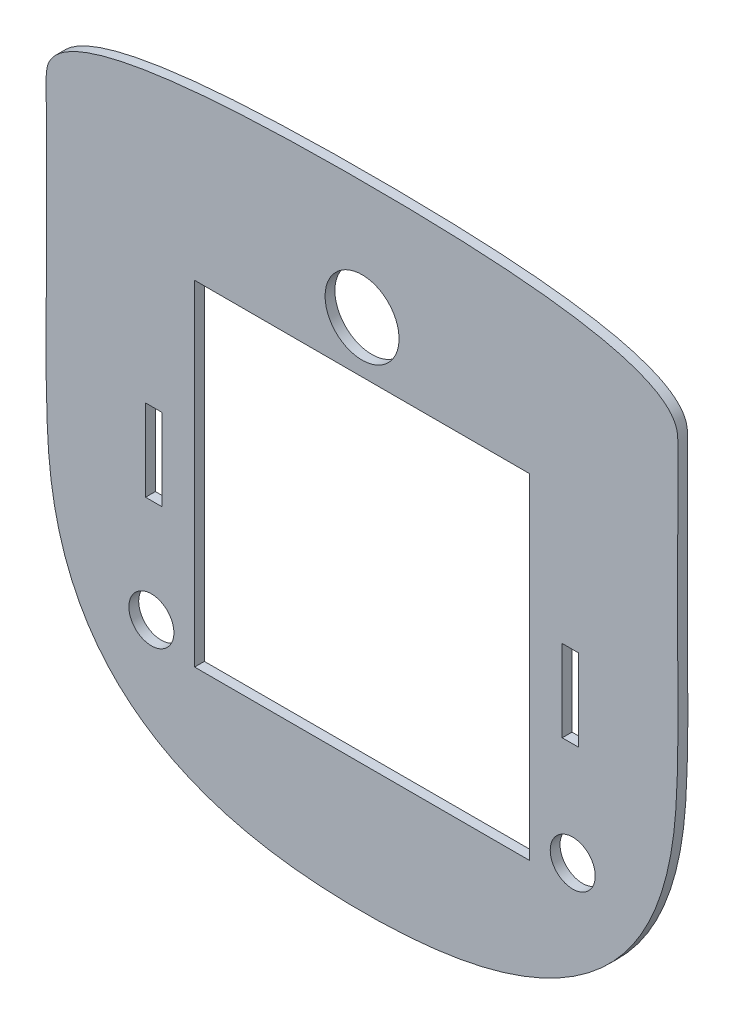
SolidWorks part; units mm, degrees
ref_plane "Front Plane" through (0, 0, 0) normal (0, 0, 1) x (1, 0, 0)
ref_plane "Top Plane" through (0, 0, 0) normal (0, 1, 0) x (1, 0, 0)
ref_plane "Right Plane" through (0, 0, 0) normal (1, 0, 0) x (0, 0, -1)
sketch "Sketch2" plane through (-0.2017, -72.2355, -2871.2971) normal (0, 0, 1) x (1, 0, 0)
  line L0 (52.07, 67.2522) -> (-52.07, 67.2522) construction
  line L1 (-52.07, 67.2522) -> (-52.07, -36.8878) construction
  line L2 (52.07, -36.8878) -> (52.07, 67.2522) construction
  line L3 (-52.07, -36.8878) -> (52.07, -36.8878) construction
  line L4 (52.07, 67.2522) -> (-52.07, 67.2522)
  line L5 (-52.07, 67.2522) -> (-52.07, -36.8878)
  line L6 (52.07, -36.8878) -> (52.07, 67.2522)
  line L7 (-52.07, -36.8878) -> (52.07, -36.8878)
  line L8 (0, 67.2522) -> (0, 47.5498)
  line L9 (-67.31, 26.6122) -> (-62.23, 26.6122)
  line L10 (-67.31, 26.6122) -> (-67.31, 1.2122)
  line L11 (-67.31, 1.2122) -> (-62.23, 1.2122)
  line L12 (-62.23, 26.6122) -> (-62.23, 1.2122)
  line L13 (67.31, 1.2122) -> (62.23, 1.2122)
  line L14 (67.31, 26.6122) -> (62.23, 26.6122)
  line L15 (62.23, 26.6122) -> (62.23, 1.2122)
  line L16 (67.31, 26.6122) -> (67.31, 1.2122)
  circle A0 centre (65.5, -30.8878) radius 7 construction
  circle A1 centre (-65.5, -30.8878) radius 7 construction
  circle A2 centre (0, 83.2872) radius 11.5 construction
  circle A3 centre (65.5, -30.8878) radius 7
  circle A4 centre (-65.5, -30.8878) radius 7
  circle A5 centre (0, 83.2872) radius 11.5
  spline S0 degree 3 poles (97.9117, 101.757) (98.0926, 100.5826) (98.1683, 99.8507) (98.201, 98.9643) (98.2056, 98.5204) (98.2033, 98.0762) (98.2036, 97.6318) (98.2026, 97.1872) (98.2018, 96.5942) (98.1997, 95.5557) (98.1964, 94.0701) (98.1912, 92.2844) (98.1853, 90.4955) (98.1786, 88.7035) (98.1713, 86.9085) (98.1636, 85.1105) (98.1554, 83.3094) (98.147, 81.5054) (98.1356, 79.096) (98.1213, 76.0769) (98.1051, 72.4424) (98.0908, 68.7965) (98.0796, 65.1394) (98.0728, 61.4713) (98.0711, 57.7925) (98.0753, 54.103) (98.0874, 50.4033) (98.1094, 46.6935) (98.1491, 41.7343) (98.2125, 35.5119) (98.2598, 28.01) (98.2502, 21.7312) (98.1939, 16.6943) (98.1345, 13.5409) (98.0699, 11.0154) (98.0125, 9.1199) (97.945, 7.2235) (97.8675, 5.3262) (97.778, 3.4282) (97.6786, 1.5298) (97.5624, -0.3688) (97.2739, -4.1659) (96.6367, -9.8576) (95.2643, -17.3922) (93.2832, -24.8169) (90.6142, -32.0401) (87.1877, -38.9585) (83.6766, -44.3599) (80.4862, -48.4025) (77.0545, -52.2409) (72.332, -56.6273) (66.103, -61.1882) (59.4287, -65.0467) (52.4324, -68.2445) (45.1957, -70.832) (37.7973, -72.8633) (30.2897, -74.3932) (22.7275, -75.4943) (12.6127, -76.4627) (5.0324, -76.7148) (-5.0355, -76.7148) (-12.6198, -76.4624) (-22.7388, -75.4931) (-30.3035, -74.391) (-37.8129, -72.8599) (-45.2125, -70.8272) (-52.4499, -68.238) (-59.4461, -65.0384) (-66.1196, -61.178) (-72.3471, -56.6154) (-77.0679, -52.2278) (-80.4981, -48.3887) (-83.6868, -44.3454) (-87.1957, -38.9438) (-90.6199, -32.0257) (-93.2868, -24.8034) (-95.2663, -17.38) (-96.6374, -9.847) (-97.2741, -4.1565) (-97.5622, -0.3603) (-97.6784, 1.5379) (-97.7779, 3.4359) (-97.8674, 5.3334) (-97.9449, 7.2303) (-98.0124, 9.1263) (-98.0698, 11.0213) (-98.1344, 13.5463) (-98.1939, 16.699) (-98.2502, 21.7349) (-98.2598, 28.0124) (-98.2124, 35.5129) (-98.1491, 41.7344) (-98.1094, 46.6929) (-98.0874, 50.4022) (-98.0753, 54.1015) (-98.0711, 57.7907) (-98.0728, 61.4693) (-98.0796, 65.1372) (-98.0908, 68.7942) (-98.1051, 72.44) (-98.1213, 76.0745) (-98.1356, 79.0937) (-98.147, 81.5032) (-98.1554, 83.3073) (-98.1636, 85.1085) (-98.1713, 86.9067) (-98.1786, 88.7018) (-98.1853, 90.494) (-98.1912, 92.283) (-98.1963, 94.069) (-98.1997, 95.5548) (-98.2018, 96.5934) (-98.2026, 97.1865) (-98.2036, 97.6312) (-98.2034, 98.0756) (-98.2056, 98.5199) (-98.201, 98.9639) (-98.1685, 99.8505) (-98.0927, 100.5825) (-97.9118, 101.7567) (-97.5911, 102.9272) (-96.7445, 104.5237) (-95.6284, 105.9307) (-94.3242, 107.1498) (-92.9089, 108.2104) (-90.9195, 109.4482) (-88.322, 110.7311) (-85.1289, 111.981) (-81.907, 113.0191) (-78.6797, 113.8993) (-75.4586, 114.6561) (-72.2483, 115.315) (-69.0513, 115.893) (-65.8677, 116.4036) (-62.6974, 116.856) (-59.5401, 117.2586) (-55.346, 117.7364) (-50.1305, 118.2378) (-43.9049, 118.7183) (-37.6983, 119.1001) (-31.4972, 119.4014) (-25.2861, 119.6319) (-19.0497, 119.8026) (-10.6783, 119.9573) (-4.3114, 120) (4.3116, 120) (10.6784, 119.9573) (19.0492, 119.8026) (25.285, 119.6319) (31.4954, 119.4014) (37.6957, 119.1003) (43.9016, 118.7185) (50.1264, 118.2381) (55.3414, 117.7368) (59.535, 117.2592) (62.6921, 116.8566) (65.8622, 116.4044) (69.0457, 115.8939) (72.2427, 115.316) (75.4529, 114.6572) (78.6742, 113.9005) (81.9018, 113.0204) (85.1241, 111.9825) (88.3177, 110.7327) (90.916, 109.4498) (92.906, 108.212) (94.3218, 107.1513) (95.6266, 105.9321) (96.7434, 104.5248) (97.5906, 102.9279) (97.9117, 101.757) (98.0926, 100.5826) (98.1683, 99.8507) knots -0.005356 -0.002678 0 0 0.002568 0.00321 0.003852 0.004494 0.005135 0.005777 0.006419 0.007703 0.010271 0.012839 0.015406 0.017974 0.020542 0.02311 0.025677 0.028245 0.030813 0.035948 0.041084 0.046219 0.051355 0.05649 0.061626 0.066761 0.071897 0.077032 0.082168 0.092439 0.10271 0.112981 0.118116 0.123252 0.125819 0.128387 0.130955 0.133522 0.13609 0.138658 0.141226 0.143793 0.154064 0.164335 0.174606 0.184877 0.195148 0.205419 0.210555 0.21569 0.225961 0.236232 0.246503 0.256774 0.267045 0.277316 0.287587 0.297858 0.308129 0.328671 0.328671 0.349207 0.359475 0.369743 0.380011 0.390279 0.400547 0.410816 0.421084 0.431352 0.44162 0.446754 0.451888 0.462156 0.472424 0.482692 0.492961 0.503229 0.513497 0.516064 0.518631 0.521198 0.523765 0.526332 0.528899 0.531466 0.534033 0.539167 0.544301 0.554569 0.564837 0.575105 0.580239 0.585374 0.590508 0.595642 0.600776 0.60591 0.611044 0.616178 0.621312 0.626446 0.629013 0.63158 0.634147 0.636714 0.639281 0.641848 0.644415 0.646982 0.649549 0.650833 0.651475 0.652116 0.652758 0.6534 0.654042 0.654683 0.65725 0.65725 0.659928 0.662606 0.665283 0.667961 0.670639 0.673317 0.678672 0.684027 0.689383 0.694738 0.700094 0.705449 0.710804 0.71616 0.721515 0.726871 0.732226 0.742937 0.753648 0.764359 0.775069 0.78578 0.796491 0.807202 0.828623 0.828623 0.850045 0.860757 0.871468 0.882179 0.89289 0.903601 0.914312 0.925023 0.930378 0.935734 0.941089 0.946445 0.9518 0.957156 0.962511 0.967867 0.973222 0.978578 0.983933 0.986611 0.989289 0.991967 0.994644 0.997322 1 1 1.002568 1.00321 1.003852 only from (98.0041, 101.1575) to (98.0041, 101.1575)
  spline S1 degree 3 poles (97.9117, 101.757) (98.0926, 100.5826) (98.1683, 99.8507) (98.201, 98.9643) (98.2056, 98.5204) (98.2033, 98.0762) (98.2036, 97.6318) (98.2026, 97.1872) (98.2018, 96.5942) (98.1997, 95.5557) (98.1964, 94.0701) (98.1912, 92.2844) (98.1853, 90.4955) (98.1786, 88.7035) (98.1713, 86.9085) (98.1636, 85.1105) (98.1554, 83.3094) (98.147, 81.5054) (98.1356, 79.096) (98.1213, 76.0769) (98.1051, 72.4424) (98.0908, 68.7965) (98.0796, 65.1394) (98.0728, 61.4713) (98.0711, 57.7925) (98.0753, 54.103) (98.0874, 50.4033) (98.1094, 46.6935) (98.1491, 41.7343) (98.2125, 35.5119) (98.2598, 28.01) (98.2502, 21.7312) (98.1939, 16.6943) (98.1345, 13.5409) (98.0699, 11.0154) (98.0125, 9.1199) (97.945, 7.2235) (97.8675, 5.3262) (97.778, 3.4282) (97.6786, 1.5298) (97.5624, -0.3688) (97.2739, -4.1659) (96.6367, -9.8576) (95.2643, -17.3922) (93.2832, -24.8169) (90.6142, -32.0401) (87.1877, -38.9585) (83.6766, -44.3599) (80.4862, -48.4025) (77.0545, -52.2409) (72.332, -56.6273) (66.103, -61.1882) (59.4287, -65.0467) (52.4324, -68.2445) (45.1957, -70.832) (37.7973, -72.8633) (30.2897, -74.3932) (22.7275, -75.4943) (12.6127, -76.4627) (5.0324, -76.7148) (-5.0355, -76.7148) (-12.6198, -76.4624) (-22.7388, -75.4931) (-30.3035, -74.391) (-37.8129, -72.8599) (-45.2125, -70.8272) (-52.4499, -68.238) (-59.4461, -65.0384) (-66.1196, -61.178) (-72.3471, -56.6154) (-77.0679, -52.2278) (-80.4981, -48.3887) (-83.6868, -44.3454) (-87.1957, -38.9438) (-90.6199, -32.0257) (-93.2868, -24.8034) (-95.2663, -17.38) (-96.6374, -9.847) (-97.2741, -4.1565) (-97.5622, -0.3603) (-97.6784, 1.5379) (-97.7779, 3.4359) (-97.8674, 5.3334) (-97.9449, 7.2303) (-98.0124, 9.1263) (-98.0698, 11.0213) (-98.1344, 13.5463) (-98.1939, 16.699) (-98.2502, 21.7349) (-98.2598, 28.0124) (-98.2124, 35.5129) (-98.1491, 41.7344) (-98.1094, 46.6929) (-98.0874, 50.4022) (-98.0753, 54.1015) (-98.0711, 57.7907) (-98.0728, 61.4693) (-98.0796, 65.1372) (-98.0908, 68.7942) (-98.1051, 72.44) (-98.1213, 76.0745) (-98.1356, 79.0937) (-98.147, 81.5032) (-98.1554, 83.3073) (-98.1636, 85.1085) (-98.1713, 86.9067) (-98.1786, 88.7018) (-98.1853, 90.494) (-98.1912, 92.283) (-98.1963, 94.069) (-98.1997, 95.5548) (-98.2018, 96.5934) (-98.2026, 97.1865) (-98.2036, 97.6312) (-98.2034, 98.0756) (-98.2056, 98.5199) (-98.201, 98.9639) (-98.1685, 99.8505) (-98.0927, 100.5825) (-97.9118, 101.7567) (-97.5911, 102.9272) (-96.7445, 104.5237) (-95.6284, 105.9307) (-94.3242, 107.1498) (-92.9089, 108.2104) (-90.9195, 109.4482) (-88.322, 110.7311) (-85.1289, 111.981) (-81.907, 113.0191) (-78.6797, 113.8993) (-75.4586, 114.6561) (-72.2483, 115.315) (-69.0513, 115.893) (-65.8677, 116.4036) (-62.6974, 116.856) (-59.5401, 117.2586) (-55.346, 117.7364) (-50.1305, 118.2378) (-43.9049, 118.7183) (-37.6983, 119.1001) (-31.4972, 119.4014) (-25.2861, 119.6319) (-19.0497, 119.8026) (-10.6783, 119.9573) (-4.3114, 120) (4.3116, 120) (10.6784, 119.9573) (19.0492, 119.8026) (25.285, 119.6319) (31.4954, 119.4014) (37.6957, 119.1003) (43.9016, 118.7185) (50.1264, 118.2381) (55.3414, 117.7368) (59.535, 117.2592) (62.6921, 116.8566) (65.8622, 116.4044) (69.0457, 115.8939) (72.2427, 115.316) (75.4529, 114.6572) (78.6742, 113.9005) (81.9018, 113.0204) (85.1241, 111.9825) (88.3177, 110.7327) (90.916, 109.4498) (92.906, 108.212) (94.3218, 107.1513) (95.6266, 105.9321) (96.7434, 104.5248) (97.5906, 102.9279) (97.9117, 101.757) (98.0926, 100.5826) (98.1683, 99.8507) knots -0.005356 -0.002678 0 0 0.002568 0.00321 0.003852 0.004494 0.005135 0.005777 0.006419 0.007703 0.010271 0.012839 0.015406 0.017974 0.020542 0.02311 0.025677 0.028245 0.030813 0.035948 0.041084 0.046219 0.051355 0.05649 0.061626 0.066761 0.071897 0.077032 0.082168 0.092439 0.10271 0.112981 0.118116 0.123252 0.125819 0.128387 0.130955 0.133522 0.13609 0.138658 0.141226 0.143793 0.154064 0.164335 0.174606 0.184877 0.195148 0.205419 0.210555 0.21569 0.225961 0.236232 0.246503 0.256774 0.267045 0.277316 0.287587 0.297858 0.308129 0.328671 0.328671 0.349207 0.359475 0.369743 0.380011 0.390279 0.400547 0.410816 0.421084 0.431352 0.44162 0.446754 0.451888 0.462156 0.472424 0.482692 0.492961 0.503229 0.513497 0.516064 0.518631 0.521198 0.523765 0.526332 0.528899 0.531466 0.534033 0.539167 0.544301 0.554569 0.564837 0.575105 0.580239 0.585374 0.590508 0.595642 0.600776 0.60591 0.611044 0.616178 0.621312 0.626446 0.629013 0.63158 0.634147 0.636714 0.639281 0.641848 0.644415 0.646982 0.649549 0.650833 0.651475 0.652116 0.652758 0.6534 0.654042 0.654683 0.65725 0.65725 0.659928 0.662606 0.665283 0.667961 0.670639 0.673317 0.678672 0.684027 0.689383 0.694738 0.700094 0.705449 0.710804 0.71616 0.721515 0.726871 0.732226 0.742937 0.753648 0.764359 0.775069 0.78578 0.796491 0.807202 0.828623 0.828623 0.850045 0.860757 0.871468 0.882179 0.89289 0.903601 0.914312 0.925023 0.930378 0.935734 0.941089 0.946445 0.9518 0.957156 0.962511 0.967867 0.973222 0.978578 0.983933 0.986611 0.989289 0.991967 0.994644 0.997322 1 1 1.002568 1.00321 1.003852 only from (98.0041, 101.1575) to (98.0041, 101.1575)
  dimension "D2" = 25.4
  dimension "D3" = 5.08
  dimension "D4" = 10.16
  dimension "D5" = 40.64
extrude "Boss-Extrude1" add sketch "Sketch2" along normal blind 3.048 contours L14 L16 L13 L15 L9 L12 L11 L10 L7 L5 L4 L6 A3 A4 A5 region at (-86.5368, -106.5692, -2871.2971)
sketch "Sketch6" plane through (0, 0, -2871.2971) normal (0, 0, -1) x (-1, 0, 0)
  line L12 (-99.7983, 25.0245) -> (-99.7983, 24.9245)
  line L13 (-99.7983, 24.9245) -> (-94.7983, 24.9245)
  line L14 (-94.7983, 24.9245) -> (-94.7983, 25.0245)
  line L15 (-94.7983, 25.0245) -> (-99.7983, 25.0245)
  line L16 (-99.7983, 25.0245) -> (-99.7983, 24.9245)
  line L17 (-99.7983, 24.9245) -> (-94.7983, 24.9245)
  line L18 (-94.7983, 24.9245) -> (-94.7983, 25.0245)
  line L19 (-94.7983, 25.0245) -> (-99.7983, 25.0245)
  dimension "D2" = 0
